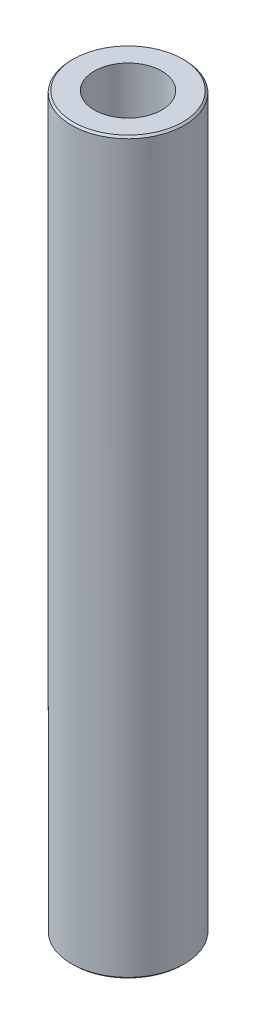
SolidWorks part; units mm, degrees
ref_plane "Front Plane" through (0, 0, 0) normal (0, 0, 1) x (1, 0, 0)
ref_plane "Top Plane" through (0, 0, 0) normal (0, 1, 0) x (1, 0, 0)
ref_plane "Right Plane" through (0, 0, 0) normal (1, 0, 0) x (0, 0, -1)
sketch "Sketch1" plane through (0, 0, 0) normal (0, 1, 0) x (1, 0, 0)
  circle A0 centre (0, 0) radius 37.5
  dimension "SHAFT_OD" = 75
extrude "Boss-Extrude1" add sketch "Sketch1" along normal blind 484.5376
sketch "Sketch2" plane through (0, 0, 0) normal (0, 1, 0) x (1, 0, 0)
  circle A0 centre (0, 0) radius 22.4098
  dimension "BORE_D" = 44.8197
extrude "Cut-Extrude1" cut sketch "Sketch2" along normal through all
chamfer "Chamfer1" distance 1.2366 angle 45 2 edges at (0, 484.5376, 37.5) (0, 0, 37.5)
